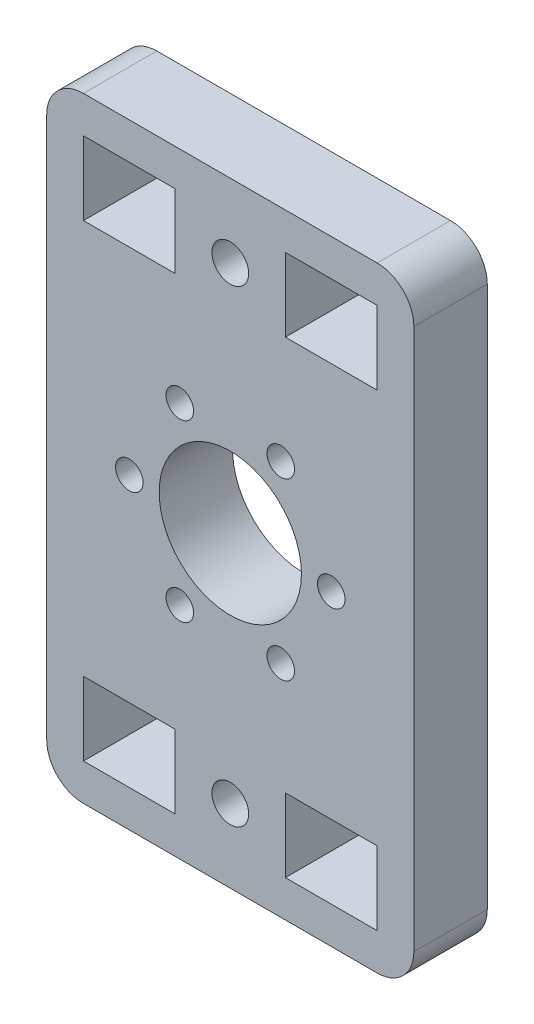
SolidWorks part; units mm, degrees
ref_plane "Front Plane" through (0, 0, 0) normal (0, 0, 1) x (1, 0, 0)
ref_plane "Top Plane" through (0, 0, 0) normal (0, 1, 0) x (1, 0, 0)
ref_plane "Right Plane" through (0, 0, 0) normal (1, 0, 0) x (0, 0, -1)
sketch "Sketch1" plane through (0, 0, 0) normal (0, 0, 1) x (1, 0, 0)
  line L0 (0, 0) -> (-11, 0) construction
  line L1 (16, -33.5) -> (-16, -33.5)
  line L2 (20, -29.5) -> (20, 29.5)
  line L3 (16, 33.5) -> (-16, 33.5)
  line L4 (-20, -29.5) -> (-20, 29.5)
  line L5 (20, -33.5) -> (-20, 33.5) construction
  line L6 (20, 33.5) -> (-20, -33.5) construction
  line L15 (0, 0) -> (0, -8.1671) construction
  line L16 (-16, -21.5) -> (-6, -21.5)
  line L17 (-16, -21.5) -> (-16, -29.5)
  line L18 (-16, -29.5) -> (-6, -29.5)
  line L19 (-6, -21.5) -> (-6, -29.5)
  line L20 (16, -29.5) -> (6, -29.5)
  line L21 (6, -21.5) -> (6, -29.5)
  line L22 (16, -21.5) -> (6, -21.5)
  line L23 (16, -21.5) -> (16, -29.5)
  line L24 (16, 21.5) -> (16, 29.5)
  line L25 (16, 21.5) -> (6, 21.5)
  line L26 (6, 21.5) -> (6, 29.5)
  line L27 (16, 29.5) -> (6, 29.5)
  line L28 (-16, 29.5) -> (-6, 29.5)
  line L29 (-6, 21.5) -> (-6, 29.5)
  line L30 (-16, 21.5) -> (-6, 21.5)
  line L31 (-16, 21.5) -> (-16, 29.5)
  circle A9 centre (0, 0) radius 7.75
  circle A10 centre (-11, 0) radius 1.5
  circle A11 centre (-5.5, 9.5263) radius 1.5
  circle A12 centre (5.5, 9.5263) radius 1.5
  circle A13 centre (11, 0) radius 1.5
  circle A14 centre (5.5, -9.5263) radius 1.5
  circle A15 centre (-5.5, -9.5263) radius 1.5
  circle A16 centre (0, -25.5) radius 2
  circle A17 centre (0, 25.5) radius 2
  arc A18 (16, -33.5) -> (20, -29.5) centre (16, -29.5) ccw
  arc A19 (-20, -29.5) -> (-16, -33.5) centre (-16, -29.5) ccw
  arc A20 (-20, 29.5) -> (-16, 33.5) centre (-16, 29.5) cw
  arc A21 (20, 29.5) -> (16, 33.5) centre (16, 29.5) ccw
  point P0 (0, 0)
  point P10 (-16, -25.5)
  dimension "D5" = 4
  dimension "D8" = 4
  dimension "D9" = 20
  dimension "D11" = 25.5
  dimension "D16" = 15.5
  dimension "D19" = 3
  dimension "D10" = 4
  dimension "D2" = 40
  dimension "D3" = 8
  dimension "D4" = 4
  dimension "D6" = 10
  dimension "D7" = 21.5
  dimension "D17" = 11
  dimension "D18" = 0
  dimension "D21" = 11
  dimension "D22" = 11
  dimension "D20" = 6
extrude "Boss-Extrude2" add sketch "Sketch1" along normal blind 8
